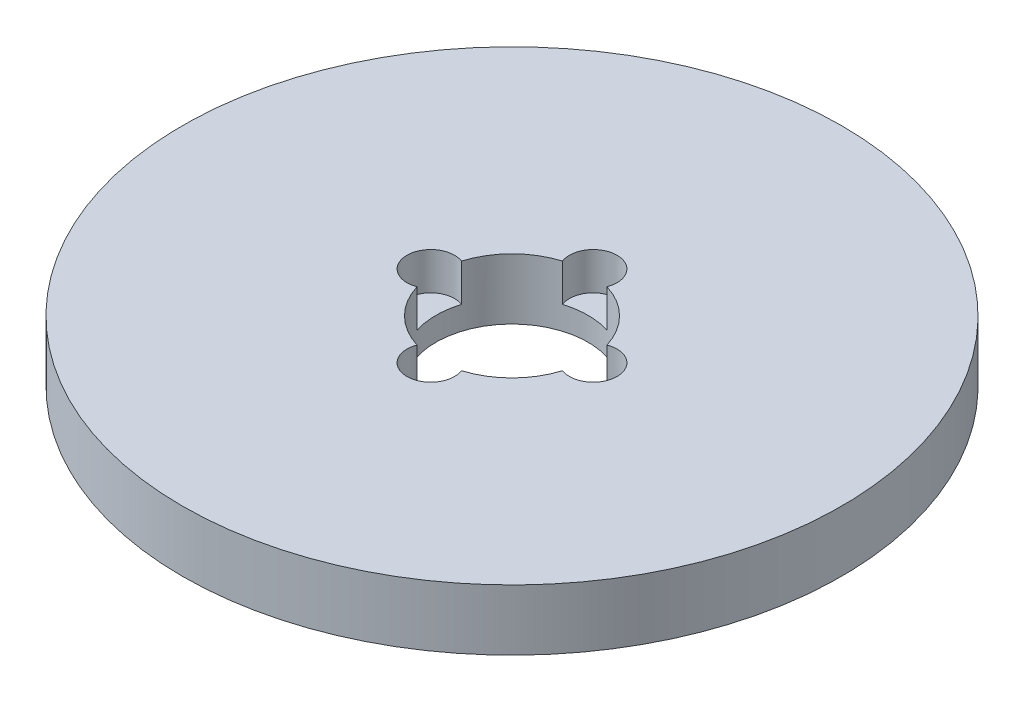
SolidWorks part; units mm, degrees
ref_plane "Front Plane" through (0, 0, 0) normal (0, 0, 1) x (1, 0, 0)
ref_plane "Top Plane" through (0, 0, 0) normal (0, 1, 0) x (1, 0, 0)
ref_plane "Right Plane" through (0, 0, 0) normal (1, 0, 0) x (0, 0, -1)
sketch "Sketch1" plane through (0, 0, 0) normal (0, 1, 0) x (1, 0, 0)
  circle A0 centre (0, 0) radius 97.5
  dimension "FLANGE_OD" = 195
extrude "Boss-Extrude1" add sketch "Sketch1" along normal blind 18
sketch "Sketch2" plane through (0, 0, 0) normal (0, 1, 0) x (1, 0, 0)
  circle A0 centre (0, 0) radius 22.5
  dimension "BORE_D" = 45
extrude "Cut-Extrude1" cut sketch "Sketch2" along normal through all
sketch "Sketch3" plane through (0, 18, 0) normal (0, 1, 0) x (1, 0, 0)
  circle A0 centre (0, 0) radius 24.0398 construction
  circle A1 centre (-24.0398, 0) radius 7.0443
  dimension "BOLT_D" = 14.0886
  dimension "BOLT_PCD" = 48.0796
extrude "Cut-Extrude2" cut sketch "Sketch3" against normal blind 11.0992
pattern_circular "CirPattern1" count 4 over 360 about axis through (0, 0, 0) along (0, 1, 0) of "Cut-Extrude2"
